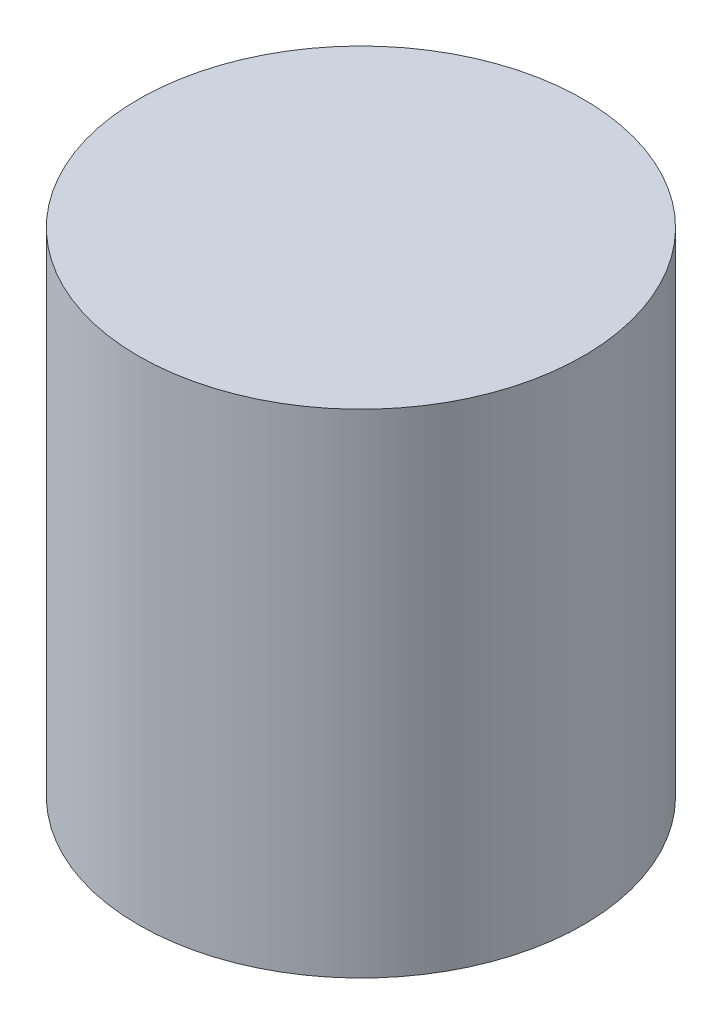
SolidWorks part; units mm, degrees
ref_plane "Front Plane" through (0, 0, 0) normal (0, 0, 1) x (1, 0, 0)
ref_plane "Top Plane" through (0, 0, 0) normal (0, 1, 0) x (1, 0, 0)
ref_plane "Right Plane" through (0, 0, 0) normal (1, 0, 0) x (0, 0, -1)
other "Bounding Box"
ref_plane "Default Plane" through (-8.9266, -12.7485, 0) normal (-0.1736, 0.9848, 0) x (0.9848, 0.1736, 0)
sketch "Sketch1" plane through (0, 0, 0) normal (0, 1, 0) x (1, 0, 0)
  circle A0 centre (0, 0) radius 14
  dimension "D1" = 28
extrude "Boss-Extrude1" add sketch "Sketch1" along normal mid plane 31
